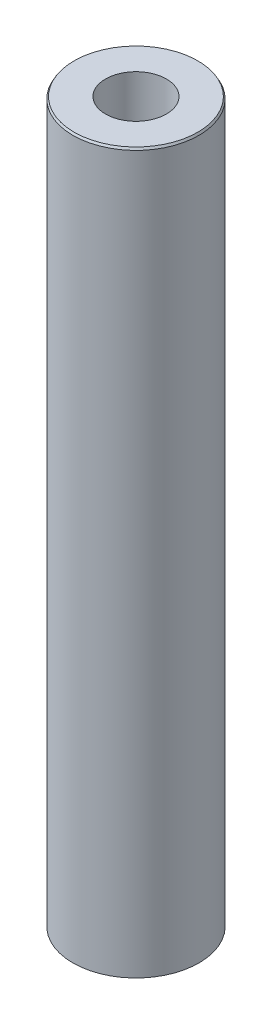
SolidWorks part; units mm, degrees
ref_plane "Front Plane" through (0, 0, 0) normal (0, 0, 1) x (1, 0, 0)
ref_plane "Top Plane" through (0, 0, 0) normal (0, 1, 0) x (1, 0, 0)
ref_plane "Right Plane" through (0, 0, 0) normal (1, 0, 0) x (0, 0, -1)
sketch "Sketch1" plane through (0, 0, 0) normal (0, 1, 0) x (1, 0, 0)
  circle A0 centre (0, 0) radius 45
  dimension "SHAFT_OD" = 90
extrude "Boss-Extrude1" add sketch "Sketch1" along normal blind 513.7379
sketch "Sketch2" plane through (0, 0, 0) normal (0, 1, 0) x (1, 0, 0)
  circle A0 centre (0, 0) radius 21.717
  dimension "BORE_D" = 43.434
extrude "Cut-Extrude1" cut sketch "Sketch2" along normal through all
chamfer "Chamfer1" distance 1.5005 angle 30 2 edges at (0, 513.7379, 45) (0, 0, 45) first distance on face at (0, 513.7379, 45) first distance on face at (0, 0, 21.717)
